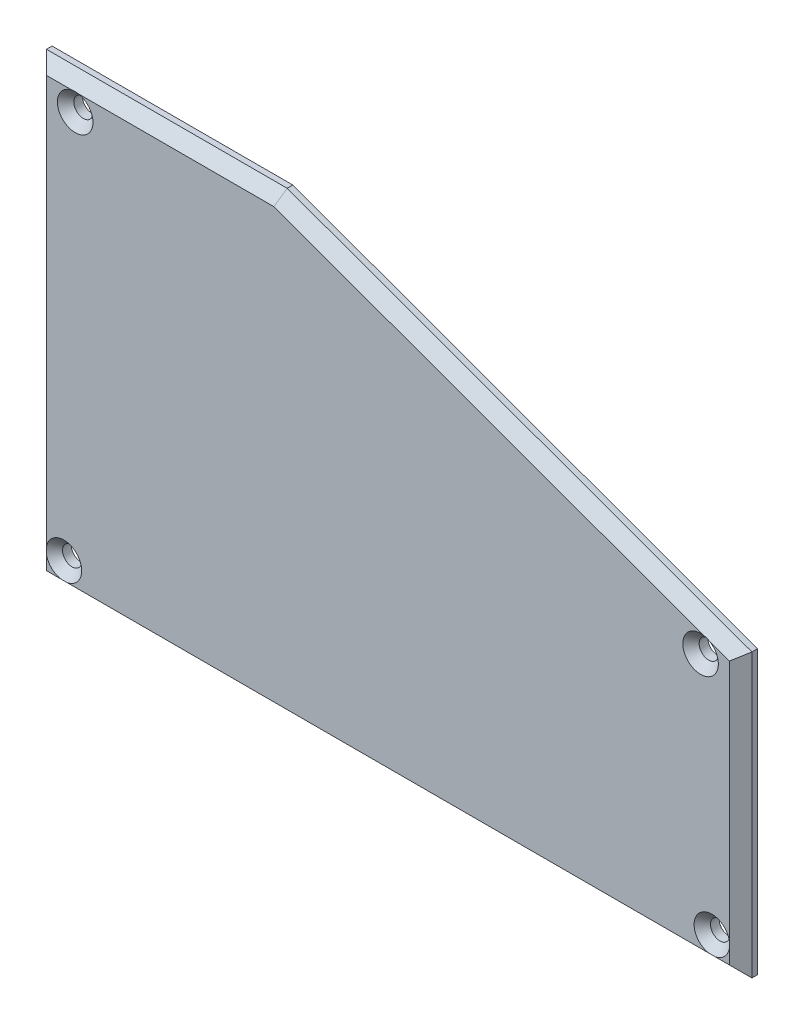
SolidWorks part; units mm, degrees
ref_plane "Спереди" through (0, 0, 0) normal (0, 0, 1) x (1, 0, 0)
ref_plane "Сверху" through (0, 0, 0) normal (0, 1, 0) x (1, 0, 0)
ref_plane "Справа" through (0, 0, 0) normal (1, 0, 0) x (0, 0, -1)
sketch "Эскиз1" plane through (0, 0, 0) normal (0, 0, 1) x (1, 0, 0)
  line L0 (-53.75, 74) -> (-11.0949, 74) construction
  line L1 (-11.0949, 74) -> (71.25, 44.0289) construction
  line L2 (71.25, 41.9283) -> (71.25, -6) construction
  line L3 (71.25, -6) -> (-53.75, -6) construction
  line L4 (-53.75, -6) -> (-53.75, 71) construction
  line L5 (-53.75, 74) -> (-11.0949, 74)
  line L6 (-11.0949, 74) -> (71.25, 44.0289)
  line L7 (71.25, 44.0289) -> (71.25, -6)
  line L8 (71.25, -6) -> (-53.75, -6)
  line L9 (-53.75, -6) -> (-53.75, 74)
extrude "Бобышка-Вытянуть1" add sketch "Эскиз1" along normal blind 3
hole_wizard "Зенковка для винта с потайной головкой M31" positions "Эскиз4" profile "Эскиз5" countersink size "M3" standard "DIN" end condition through all
sketch "Эскиз4" plane through (0, 0, 3) normal (0, 0, 1) x (1, 0, 0)
  point P0 (-46.65, 68.9)
  point P3 (-48.65, -0.9)
  point P7 (64.15, 41.1858)
  point P10 (66.15, -0.9)
sketch "Эскиз5" plane through (-46.65, 68.9, 3) normal (1, 0, 0) x (0, -1, 0)
  line L0 (0, 0) -> (0, 3)
  line L1 (0, 3) -> (1.7, 3)
  line L2 (1.7, 3) -> (1.7, 1.45)
  line L3 (1.7, 1.45) -> (3.15, 0)
  line L5 (3.15, 0) -> (0, 0)
  line L6 (-1.7, 1.45) -> (-3.15, 0) construction
  line L11 (0, -6.35) -> (0, 107.95) construction
  dimension "Диаметр сквозного отверстия" = 3.4
  dimension "Глубина сквозного отверстия" = 3
  dimension "Диаметр передней зенковки" = 6.3
  dimension "Угол передней зенковки" = 90
chamfer "Фаска1" distance 2 angle 45 5 edges at (-32.4224, 74, 3) (-53.75, 34, 3) (8.75, -6, 3) (71.25, 19.0145, 3) (30.0776, 59.0145, 3)
